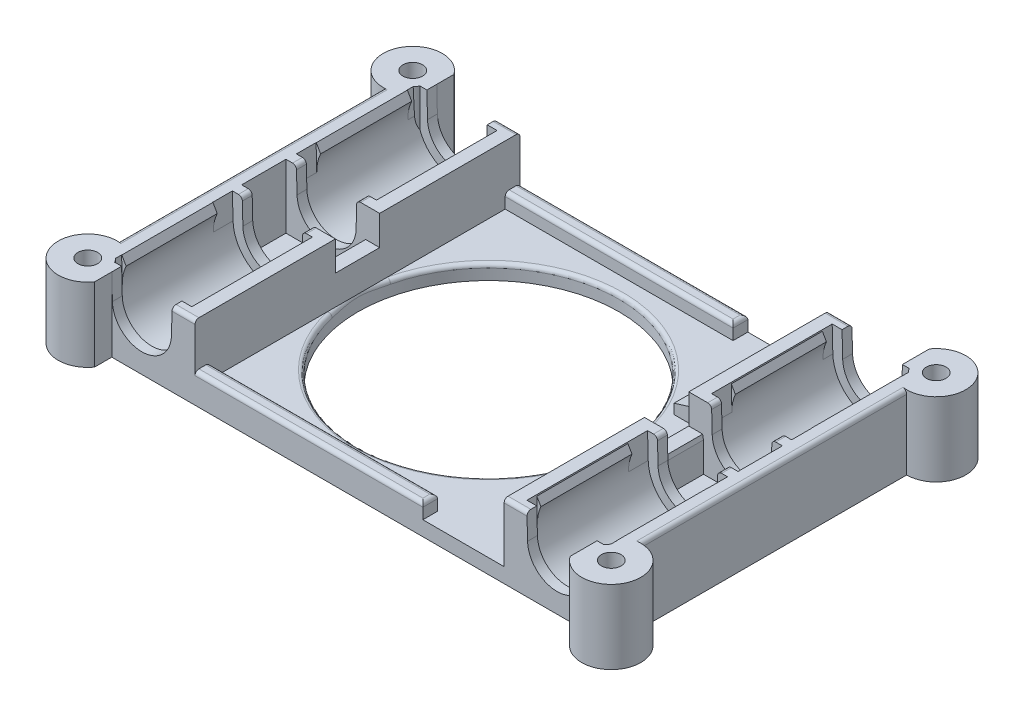
SolidWorks part; units mm, degrees
ref_plane "Front" through (0, 0, 0) normal (0, 0, 1) x (1, 0, 0)
ref_plane "Top" through (0, 0, 0) normal (0, 1, 0) x (1, 0, 0)
ref_plane "Right" through (0, 0, 0) normal (1, 0, 0) x (0, 0, -1)
sketch "Sketch1" plane through (0, 0, 0) normal (0, 1, 0) x (1, 0, 0)
  line L1 (-62.38, 33) -> (62.38, 33)
  line L2 (-62.38, 33) -> (-62.38, -33)
  line L3 (-62.38, -33) -> (62.38, -33)
  line L4 (62.38, 33) -> (62.38, -33)
  dimension "D1" = 124.76
  dimension "D2" = 66
  dimension "6" = 62.38
  dimension "D4" = 33
extrude "Boss-Extrude1" add sketch "Sketch1" along normal blind 20
sketch "Sketch2" plane through (0, 0, 33) normal (0, 0, 1) x (1, 0, 0)
  line L0 (-62.38, 0) -> (62.38, 0) construction
  line L1 (-62.38, 20) -> (-62.38, 0) construction
  line L2 (62.38, 20) -> (62.38, 0) construction
  circle A0 centre (-42.16, 10) radius 8
  circle A1 centre (42.16, 10) radius 8
  dimension "D2" = 16
  dimension "D3" = 16
  dimension "D1" = 20.22
  dimension "D4" = 10
  dimension "D5" = 10
  dimension "D6" = 20.22
  dimension "D7" = 84.32
extrude "Cut-Extrude1" cut sketch "Sketch2" against normal through all
sketch "Sketch4" plane through (-62.38, 0, 0) normal (-1, 0, 0) x (0, 0, 1)
  line L0 (-33, 20) -> (33, 20) construction
  line L1 (31, 2) -> (-31, 2)
  line L2 (31, 2) -> (31, 20)
  line L3 (31, 20) -> (-31, 20)
  line L4 (-31, 2) -> (-31, 20)
  line L5 (-33, 0) -> (33, 0) construction
  line L6 (33, 2) -> (33, 18) construction
  line L9 (-33, 20) -> (-33, 0) construction
  dimension "D1" = 2
  dimension "D2" = 2
  dimension "D3" = 2
extrude "Cut-Extrude2" cut sketch "Sketch4" against normal blind 27.98
sketch "Sketch5" plane through (62.38, 0, 0) normal (1, 0, 0) x (0, 0, -1)
  line L0 (-33, 20) -> (33, 20) construction
  line L1 (-31, 2) -> (31, 2)
  line L2 (-31, 2) -> (-31, 20)
  line L3 (-31, 20) -> (31, 20)
  line L4 (31, 2) -> (31, 20)
  line L5 (-33, 0) -> (33, 0) construction
  line L6 (-33, 20) -> (-33, 0) construction
  line L7 (33, 20) -> (33, 0) construction
  dimension "D1" = 2
  dimension "D2" = 2
  dimension "D3" = 2
extrude "Cut-Extrude3" cut sketch "Sketch5" against normal blind 27.98
sketch "Sketch6" plane through (0, 0, 31) normal (0, 0, -1) x (-1, 0, 0)
  line L0 (34.4, 20) -> (62.38, 20) construction
  line L1 (31.16, 20) -> (53.16, 20)
  line L2 (31.16, 20) -> (31.16, 1.5)
  line L3 (31.16, 1.5) -> (53.16, 1.5)
  line L4 (53.16, 20) -> (53.16, 1.5)
  circle A0 centre (42.16, 10) radius 8 construction
  circle A1 centre (42.16, 10) radius 8
  dimension "D1" = 22
  dimension "D2" = 11
  dimension "D3" = 18.5
extrude "Boss-Extrude2" add sketch "Sketch6" along normal blind 24.5
mirror "Mirror1" about plane through (0, 0, 0) normal (0, 0, 1) of "Boss-Extrude2"
mirror "Mirror2" about plane through (0, 0, 0) normal (1, 0, 0) of "Mirror1", "Boss-Extrude2"
sketch "Sketch7" plane through (0, 0, 33) normal (0, 0, 1) x (1, 0, 0)
  line L0 (34.1625, 9.8) -> (33.9074, 20)
  line L2 (-62.38, 20) -> (62.38, 20) construction
  line L3 (33.9074, 20) -> (50.4126, 20)
  line L4 (50.4126, 20) -> (50.1575, 9.8)
  circle A1 centre (42.16, 10) radius 8 construction
  arc A2 (34.1625, 9.8) -> (50.1575, 9.8) centre (42.16, 10) ccw
  dimension "D1" = 0.2
  dimension "D2" = 0.2
extrude "Cut-Extrude4" cut sketch "Sketch7" against normal blind 4
mirror "Mirror3" about plane through (0, 0, 0) normal (1, 0, 0) of "Cut-Extrude4"
mirror "Mirror4" about plane through (0, 0, 0) normal (0, 0, 1) of "Mirror3", "Cut-Extrude4"
sketch "Sketch8" plane through (0, 0, -6.5) normal (0, 0, 1) x (1, 0, 0)
  line L0 (50.1575, 9.8) -> (50.4126, 20) construction
  line L1 (33.9074, 20) -> (34.1625, 9.8) construction
  line L2 (50.1575, 9.8) -> (50.4126, 20)
  line L3 (33.9074, 20) -> (34.1625, 9.8)
  line L4 (50.4126, 20) -> (33.9074, 20)
  arc A0 (34.1625, 9.8) -> (50.1575, 9.8) centre (42.16, 10) ccw construction
  arc A1 (34.1625, 9.8) -> (50.1575, 9.8) centre (42.16, 10) ccw
extrude "Cut-Extrude5" cut sketch "Sketch8" against normal blind 4
mirror "Mirror5" about plane through (0, 0, 0) normal (1, 0, 0) of "Cut-Extrude5"
mirror "Mirror6" about plane through (0, 0, 0) normal (0, 0, 1) of "Mirror5", "Cut-Extrude5"
sketch "Sketch10" plane through (0, 0, -29) normal (0, 0, -1) x (-1, 0, 0)
  line L0 (34.0395, 14.7187) -> (34.8653, 13.2845)
  line L1 (50.1575, 9.8) -> (50.4126, 20) construction
  line L2 (50.2893, 15.07) -> (50.4126, 20)
  line L3 (50.4126, 20) -> (33.9074, 20)
  line L4 (33.9074, 20) -> (34.0395, 14.7187)
  line L5 (33.9074, 20) -> (34.1625, 9.8) construction
  line L7 (49.3681, 13.4703) -> (50.2893, 15.07)
  arc A0 (50.1575, 9.8) -> (34.1625, 9.8) centre (42.16, 10) ccw construction
  arc A1 (49.3681, 13.4703) -> (34.8653, 13.2845) centre (42.16, 10) ccw
  dimension "D2" = 151.498
  dimension "D1" = 151.498
extrude "Cut-Extrude6" cut sketch "Sketch10" against normal through all both and the other way through all
mirror "Mirror7" about plane through (0, 0, 0) normal (1, 0, 0) of "Cut-Extrude6"
ref_plane "Plane6" through (0, 10, 0) normal (0, 1, 0) x (1, 0, 0)
sketch "Sketch12" plane through (0, 0, -33) normal (0, 0, -1) x (-1, 0, 0)
  line L2 (48.4132, 20.05) -> (62.38, 20)
  line L3 (62.38, 20) -> (62.38, 0)
  line L4 (35.9068, 20.05) -> (36.1619, 9.85)
  line L5 (48.1581, 9.85) -> (48.4132, 20.05)
  line L6 (35.9068, 20.05) -> (36.1619, 9.85)
  line L7 (48.1581, 9.85) -> (48.4132, 20.05)
  line L8 (62.38, 0) -> (30.8026, 0)
  line L9 (-62.38, 0) -> (62.38, 0) construction
  line L10 (30.8026, 0) -> (30.8026, 20)
  line L11 (-33.9074, 20) -> (33.9074, 20) construction
  line L12 (30.8026, 20) -> (35.9068, 20.05)
  arc A2 (36.1619, 9.85) -> (48.1581, 9.85) centre (42.16, 10) ccw
  arc A3 (36.1619, 9.85) -> (48.1581, 9.85) centre (42.16, 10) ccw
  dimension "D1" = 2
extrude "Boss-Extrude3" add sketch "Sketch12" against normal blind 2
mirror "Mirror10" about plane through (0, 0, 0) normal (1, 0, 0) of "Boss-Extrude3"
mirror "Mirror11" about plane through (0, 0, 0) normal (0, 0, 1) of "Boss-Extrude3", "Mirror10"
sketch "Sketch13" plane through (0, 0, 6.5) normal (0, 0, -1) x (-1, 0, 0)
  line L0 (48.4132, 20.05) -> (48.1581, 9.85) construction
  line L1 (36.1619, 9.85) -> (35.9068, 20.05) construction
  line L2 (48.4132, 20.05) -> (48.1581, 9.85)
  line L3 (36.1619, 9.85) -> (35.9068, 20.05)
  line L4 (50.4126, 20) -> (48.4132, 20.05)
  line L5 (50.4126, 20) -> (53.16, 20)
  line L6 (53.16, 20) -> (53.16, 2)
  line L7 (42.16, 2) -> (53.16, 2) construction
  line L8 (53.16, 2) -> (28.78, 2)
  line L9 (28.78, 2) -> (28.78, 20)
  line L11 (28.78, 20) -> (35.9068, 20.05)
  arc A0 (36.1619, 9.85) -> (48.1581, 9.85) centre (42.16, 10) ccw construction
  arc A1 (36.1619, 9.85) -> (48.1581, 9.85) centre (42.16, 10) ccw
  dimension "D1" = 24.38
extrude "Boss-Extrude4" add sketch "Sketch13" along normal blind 2
mirror "Mirror12" about plane through (0, 0, 0) normal (1, 0, 0) of "Boss-Extrude4"
mirror "Mirror13" about plane through (0, 0, 0) normal (0, 0, 1) of "Mirror12", "Boss-Extrude4"
sketch "Sketch14" plane through (0, 0, 0) normal (0, -1, 0) x (1, 0, 0)
  line L0 (53.16, 4.5) -> (53.16, 31) construction
  line L1 (53.16, -33) -> (53.16, 33)
  line L2 (-62.38, 33) -> (62.38, 33) construction
  line L3 (62.38, 33) -> (62.38, -33) construction
  line L4 (62.38, 33) -> (62.38, -33)
  line L5 (53.16, 33) -> (62.38, 33)
  line L6 (53.16, -33) -> (62.38, -33)
extrude "Cut-Extrude9" cut sketch "Sketch14" against normal through all
mirror "Mirror15" about plane through (0, 0, 0) normal (1, 0, 0) of "Cut-Extrude9"
sketch "Sketch15" plane through (0, 20, 0) normal (0, 1, 0) x (1, 0, 0)
  line L0 (31.4, -33) -> (31.4, 33)
  line L1 (-30.8026, -33) -> (30.8026, -33) construction
  line L2 (30.8026, 33) -> (-30.8026, 33) construction
  line L3 (53.16, -4.5) -> (53.16, 4.5) construction
  line L4 (-31.38, -33) -> (-31.38, 33)
  line L5 (-31.38, 33) -> (31.4, 33)
  line L6 (31.4, -33) -> (-31.38, -33)
  dimension "D1" = 21.76
  dimension "D2" = 62.78
extrude "Cut-Extrude10" cut sketch "Sketch15" against normal blind 17
sketch "Sketch16" plane through (0, 2, 0) normal (0, 1, 0) x (1, 0, 0)
  line L2 (-53.16, 4.5) -> (-53.16, -4.5)
  line L3 (-53.16, -4.5) -> (-50.4126, -4.5)
  line L4 (-34.4, -4.5) -> (-53.16, -4.5) construction
  line L5 (-53.16, 4.5) -> (-50.4126, 4.5)
  line L6 (-50.4126, 6.5) -> (-50.4126, 31) construction
  line L7 (-50.4126, -4.5) -> (-50.4126, 4.5)
extrude "Boss-Extrude6" add sketch "Sketch16" along normal up to vertex (18 mm away)
mirror "Mirror16" about plane through (0, 0, 0) normal (1, 0, 0) of "Boss-Extrude6"
sketch "Sketch17" plane through (53.16, 0, 0) normal (1, 0, 0) x (0, 0, -1)
  line L0 (20.9433, 20) -> (10.8, 11)
  line L1 (10.8, 11) -> (-9.9399, 11)
  line L2 (-9.9399, 11) -> (-20.9009, 20)
  line L3 (31, 20) -> (-31, 20) construction
  line L4 (50, 10) -> (-50, 10) construction
  line L5 (20.9433, 20) -> (-20.9009, 20)
  dimension "D1" = 1
extrude "Cut-Extrude11" [suppressed] cut sketch "Sketch17" against normal blind 16
mirror "Mirror17" [suppressed] about plane through (0, 0, 0) normal (1, 0, 0)
sketch "Sketch18" plane through (0, 0, 0) normal (0, -1, 0) x (1, 0, 0)
  line L1 (22.4, 8) -> (22.4, 23)
  line L2 (31.4, 33) -> (31.4, -33) construction
  line L3 (31.4, 23) -> (31.4, 8)
  line L5 (31.4, 23) -> (22.4, 23)
  line L6 (50, 0) -> (-50, 0) construction
  line L7 (22.4, 8) -> (31.4, 8)
  dimension "D1" = 23
  dimension "D2" = 15
  dimension "D3" = 9
extrude "Cut-Extrude12" [suppressed] cut sketch "Sketch18" against normal blind 25
mirror "Mirror18" [suppressed] about plane through (0, 0, 0) normal (0, 0, 1)
sketch "Sketch19" plane through (31.4, 0, 0) normal (-1, 0, 0) x (0, 0, 1)
  line L1 (-21.5, 6.5) -> (-9.5, 6.5)
  line L2 (-21.5, 6.5) -> (-21.5, 4.5)
  line L3 (-21.5, 4.5) -> (-9.5, 4.5)
  line L4 (-9.5, 6.5) -> (-9.5, 4.5)
  line L7 (33, 3) -> (-33, 3) construction
  line L8 (-33, 3) -> (-33, 20) construction
  dimension "D1" = 11.5
  dimension "D2" = 2
  dimension "D3" = 12
  dimension "D4" = 1.5
extrude "Boss-Extrude7" add sketch "Sketch19" along normal blind 8
mirror "Mirror19" about plane through (0, 0, 0) normal (0, 0, 1) of "Boss-Extrude7"
sketch "Sketch21" plane through (0, 20, 0) normal (0, 1, 0) x (1, 0, 0)
  line L2 (-34.4, 4.5) -> (-34.4, -4.5) construction
  line L6 (-30.8026, 33) -> (-31.38, 33) construction
  circle A0 centre (-4.77, 0) radius 26.5
  dimension "D1" = 53
  dimension "D2" = 29.63
  dimension "D3" = 33
extrude "Cut-Extrude13" cut sketch "Sketch21" against normal through all
sketch "Sketch23" plane through (0, 0, 33) normal (0, 0, 1) x (1, 0, 0)
  line L0 (-53.16, 20.5) -> (53.16, 20.5)
  line L2 (-53.16, 0) -> (53.16, 0) construction
  line L3 (53.16, 15) -> (-53.16, 15)
  line L4 (53.16, 20.033) -> (53.16, 0) construction
  line L6 (-53.16, 20.033) -> (-53.16, 0) construction
  line L7 (-53.16, 15) -> (-53.16, 20.5)
  line L8 (53.16, 15) -> (53.16, 20.5)
  dimension "D1" = 15
  dimension "D2" = 5.5
extrude "Cut-Extrude18" cut sketch "Sketch23" against normal through all
sketch "Sketch27" plane through (-31.38, 0, 0) normal (1, 0, 0) x (0, 0, -1)
  line L2 (-4.5, 15) -> (-4.5, 8.98)
  line L3 (4.5, 8.98) -> (4.5, 15)
  line L5 (4.5, 15) -> (-4.5, 15)
  line L8 (4.5, 8.98) -> (-4.5, 8.98)
  line L10 (33, 15) -> (-33, 15) construction
  line L11 (-4.5, 14.0926) -> (-4.5, 11.9448) construction
  line L12 (4.5, 2) -> (4.5, 8.0552) construction
  dimension "D1" = 6.02
extrude "Cut-Extrude20" cut sketch "Sketch27" against normal blind 6
sketch "Sketch28" plane through (34.4, 0, 0) normal (1, 0, 0) x (0, 0, -1)
  line L0 (4.5, 2) -> (4.5, 8.0552) construction
  line L1 (-4.5, 15) -> (4.5, 15)
  line L2 (-4.5, 15) -> (-4.5, 8.98)
  line L3 (-4.5, 8.98) -> (4.5, 8.98)
  line L4 (4.5, 15) -> (4.5, 8.98)
  line L5 (-4.5, 14.0926) -> (-4.5, 11.9448) construction
  dimension "D1" = 6.02
extrude "Cut-Extrude21" cut sketch "Sketch28" against normal blind 6
sketch "Sketch29" plane through (0, 3, 0) normal (0, 1, 0) x (1, 0, 0)
  line L0 (-31.38, 33) -> (-31.38, -33) construction
  line L2 (31.4, 33) -> (-31.38, 33) construction
  line L3 (14.8966, 33) -> (-31.38, 33)
  line L5 (-31.38, -33) -> (31.4, -33) construction
  line L6 (-31.38, -33) -> (14.8966, -33)
  line L7 (-31.38, -30) -> (-31.38, -33)
  line L8 (-31.38, 33) -> (-31.38, 30)
  line L26 (14.8966, 30) -> (14.8966, 33)
  line L29 (14.8966, -33) -> (14.8966, -30)
  line L33 (-31.38, -30) -> (14.8966, -30)
  line L35 (14.8966, 30) -> (-31.38, 30)
  point P11 (18.4, 23)
  point P12 (18.4, 33)
  point P36 (19.4, 5)
  point P37 (27.38, 5)
  point P38 (24.38, 8)
  point P39 (21.9, -5)
  dimension "D1" = 46.2766
  dimension "D2" = 3
  dimension "D3" = 3
sketch "Sketch30" plane through (0, 0, 0) normal (0, -1, 0) x (1, 0, 0)
  line L1 (-53.16, 33) -> (53.16, 33) construction
  line L2 (-53.16, 33) -> (-53.16, -33) construction
  line L3 (-53.16, 33) -> (-49.16, 33)
  line L4 (-53.16, 33) -> (-53.16, 29)
  arc A0 (-49.16, 33) -> (-53.16, 29) centre (-53.16, 33) cw
  dimension "D1" = 4
extrude "Boss-Extrude11" add sketch "Sketch29" along normal blind 3
extrude "Cut-Extrude24" cut sketch "Sketch30" against normal through all
mirror "Mirror20" about plane through (0, 0, 0) normal (0, 0, 1) of "Cut-Extrude24"
mirror "Mirror21" about plane through (0, 0, 0) normal (1, 0, 0) of "Mirror20", "Cut-Extrude24"
ref_plane "Plane7" through (31.4, 6.5, 9.5) normal (0, 0, 1) x (1, 0, 0)
sketch "Sketch32" plane through (31.4, 6.5, 9.5) normal (0, 0, 1) x (1, 0, 0)
  line L0 (-8, 0) -> (0, 2.48)
  line L1 (-8, 0) -> (0, 0) construction
  line L2 (0, 0) -> (0, 3.7007) construction
rib "Rib1" sketch "Sketch32" sketch "Sketch32" thickness 12 parameters "D1"=12
mirror "Mirror22" about plane through (0, 0, 0) normal (0, 0, 1) of "Rib1"
sketch "Sketch36" plane through (31.4, 0, 0) normal (-1, 0, 0) x (0, 0, 1)
  line L0 (15.015, 4.1169) -> (14.9192, 4.5)
  line L1 (15.5, 4.5) -> (15.5, -6.0947) construction
  line L2 (21.5, 4.5) -> (9.5, 4.5) construction
  line L3 (15.985, 4.1169) -> (16.0808, 4.5)
  line L4 (14.9192, 4.5) -> (16.0808, 4.5)
  arc A0 (15.015, 4.1169) -> (15.985, 4.1169) centre (15.5, 4.2382) ccw
  dimension "D1" = 1.1617
  dimension "D2" = 28.082
  dimension "D3" = 0.3831
extrude "Boss-Extrude8" add sketch "Sketch36" along normal up to surface (8 mm away) up to face at (23.4, 5.5, 15.5)
pattern_linear "LPattern1" count 3 spacing 2 along (0, 0, 1) count 3 spacing 2 along (0, 0, -1) of "Boss-Extrude8"
mirror "Mirror23" about plane through (0, 0, 0) normal (0, 0, 1) of "LPattern1", "Boss-Extrude8"
sketch "Sketch40" plane through (0, 2, 0) normal (0, 1, 0) x (1, 0, 0)
  line L0 (0, 0) -> (19.5479, 0) construction
  line L2 (50.4126, -4.5) -> (50.4126, 4.5) construction
  line L3 (-50.4126, -4.5) -> (-50.4126, 4.5) construction
  circle A0 centre (42.5776, 0) radius 2.375
  circle A1 centre (-42.5776, 0) radius 2.375
  dimension "D1" = 4.75
  dimension "D2" = 7.835
  dimension "D3" = 4.75
  dimension "D4" = 7.835
extrude "Cut-Extrude27" cut sketch "Sketch40" against normal up to next
sketch "Sketch37" plane through (0, 0, 0) normal (0, -1, 0) x (1, 0, 0)
  line L0 (-49.16, 33) -> (49.16, 33) construction
  line L1 (11.16, 33) -> (13.23, 33)
  line L2 (11.16, 33) -> (11.16, 30.93)
  line L3 (11.16, 30.93) -> (13.23, 30.93)
  line L4 (13.23, 33) -> (13.23, 30.93)
  line L5 (49.16, -33) -> (-49.16, -33) construction
  line L6 (-22.77, 33) -> (-24.84, 33)
  line L7 (-22.77, 33) -> (-22.77, 30.93)
  line L8 (-22.77, 30.93) -> (-24.84, 30.93)
  line L9 (-24.84, 33) -> (-24.84, 30.93)
  line L10 (11.16, -33) -> (13.23, -33)
  line L11 (11.16, -33) -> (11.16, -30.93)
  line L12 (11.16, -30.93) -> (13.23, -30.93)
  line L13 (13.23, -33) -> (13.23, -30.93)
  line L14 (53.16, 29) -> (53.16, -29) construction
  line L15 (-22.77, -33) -> (-24.84, -33)
  line L16 (-22.77, -33) -> (-22.77, -30.93)
  line L17 (-22.77, -30.93) -> (-24.84, -30.93)
  line L18 (-24.84, -33) -> (-24.84, -30.93)
  circle A0 centre (-4.77, 0) radius 26.5 construction
  dimension "D1" = 42
  dimension "D2" = 36
  dimension "D3" = 18
  dimension "D4" = 2.07
extrude "Boss-Extrude9" [suppressed] add sketch "Sketch37" along normal blind 3
sketch "Sketch39" plane through (0, 0, 0) normal (0, -1, 0) x (1, 0, 0)
  line L0 (-53.16, 29) -> (-53.16, -29) construction
  line L1 (49.16, -33) -> (-49.16, -33) construction
  line L2 (-49.16, 33) -> (49.16, 33) construction
  circle A0 centre (21.1, 26) radius 2.175
  circle A1 centre (-18.9, 26) radius 2.175
  circle A2 centre (21.1, -26) radius 2.175
  circle A3 centre (-18.9, -26) radius 2.175
  dimension "D1" = 7
  dimension "D3" = 40
  dimension "D5" = 4.35
  dimension "D2" = 7
  dimension "D4" = 34.26
extrude "Cut-Extrude26" [suppressed] cut sketch "Sketch39" against normal up to next
sketch "Sketch38" plane through (0, 0, 0) normal (0, -1, 0) x (1, 0, 0)
  line L0 (53.16, 29) -> (53.16, -29) construction
  line L1 (49.96, 10.8) -> (45.36, 10.8)
  line L2 (49.96, 10.8) -> (49.96, 5.7)
  line L3 (49.96, 5.7) -> (45.36, 5.7)
  line L4 (45.36, 10.8) -> (45.36, 5.7)
  line L6 (-43.36, 10.8) -> (-46.96, 10.8)
  line L7 (-43.36, 10.8) -> (-43.36, -10.8)
  line L8 (-43.36, -10.8) -> (-46.96, -10.8)
  line L9 (-46.96, 10.8) -> (-46.96, -10.8)
  line L10 (-53.16, 29) -> (-53.16, -29) construction
  circle A0 centre (-4.77, 0) radius 26.5 construction
  dimension "D3" = 10.8
  dimension "D7" = 10.8
  dimension "D1" = 5.1
  dimension "D2" = 4.6
  dimension "D4" = 3.2
  dimension "D5" = 21.6
  dimension "D6" = 3.6
  dimension "D8" = 9.8
extrude "Boss-Extrude10" [suppressed] add sketch "Sketch38" along normal blind 2.7
sketch "Sketch44" plane through (0, 15, 0) normal (0, 1, 0) x (1, 0, 0)
  line L0 (-53.16, 29) -> (-53.16, -29) construction
  line L1 (-53.16, -33) -> (-53.16, -29)
  line L2 (-49.16, -33) -> (-53.16, -33)
  line L3 (-48.2869, -33) -> (-48.2869, -36.5004)
  line L4 (47.16, -33) -> (53.16, -33)
  line L5 (53.16, -33) -> (53.16, -27)
  line L6 (-49.16, -33) -> (-47.16, -33)
  line L7 (48.2869, -33) -> (48.2869, -36.5004)
  line L8 (-53.16, -29) -> (-53.16, -27)
  line L9 (47.16, 33) -> (53.16, 33)
  line L10 (53.16, 33) -> (53.16, 27)
  line L11 (48.2869, 33) -> (48.2869, 36.5004)
  line L13 (-53.16, 27) -> (-53.16, 33)
  line L14 (-53.16, 33) -> (-47.16, 33)
  line L16 (-48.2869, 33) -> (-48.2869, 36.5004)
  circle A0 centre (-53.16, -33) radius 6
  circle A1 centre (-53.16, 33) radius 6
  circle A2 centre (53.16, 33) radius 6
  circle A3 centre (53.16, -33) radius 6
  arc A4 (-49.16, -33) -> (-53.16, -29) centre (-53.16, -33) ccw
  arc A6 (-53.16, 29) -> (-49.16, 33) centre (-53.16, 33) ccw
  arc A7 (53.16, 29) -> (49.16, 33) centre (53.16, 33) cw
  arc A8 (53.16, -29) -> (49.16, -33) centre (53.16, -33) ccw
  circle A9 centre (53.16, 33) radius 2
  circle A10 centre (53.16, -33) radius 2
  circle A11 centre (-53.16, -33) radius 2
  circle A12 centre (-53.16, 33) radius 2
extrude "Boss-Extrude14" add sketch "Sketch44" against normal blind 15
fillet "Fillet1" radius 0.8 6 edges at (-33.7065, 15, 33) (33.7165, 15, -33) (-33.7065, 15, -33) (33.7165, 15, 33) (-53.16, 15, 0) (53.16, 15, 0)
fillet "Fillet2" radius 0.8 15 edges at (36.0331, 15, -5.5) (-36.0331, 15, 5.5) (36.0331, 15, 5.5) (48.2869, 15, 5.5) (-48.2869, 15, -5.5) (-36.0331, 15, -5.5) (48.2869, 15, -5.5) (-48.2869, 15, 5.5) (-8.2417, 6, 30) (-8.2417, 6, 33) (14.8966, 6, 31.5) (-8.2417, 6, -30) (14.8966, 6, -31.5) (-8.2417, 6, -33) (-4.77, 3, -26.5)
